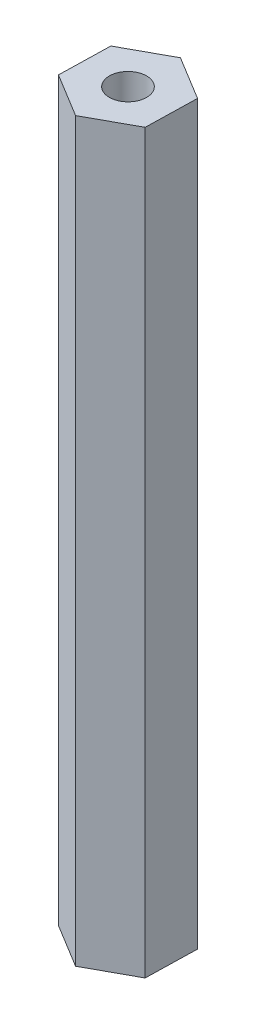
SolidWorks part; units mm, degrees
material "AISI 316 Annealed Stainless Steel Bar (SS)"
ref_plane "Front Plane" through (0, 0, 0) normal (0, 0, 1) x (1, 0, 0)
ref_plane "Top Plane" through (0, 0, 0) normal (0, 1, 0) x (1, 0, 0)
ref_plane "Right Plane" through (0, 0, 0) normal (1, 0, 0) x (0, 0, -1)
sketch "Sketch1" plane through (0, 0, 0) normal (0, 1, 0) x (1, 0, 0)
  line L1 (5.0651, 2.7709) -> (0.1329, 5.772)
  line L2 (0.1329, 5.772) -> (-4.9322, 3.0011)
  line L3 (-4.9322, 3.0011) -> (-5.0651, -2.7709)
  line L4 (-5.0651, -2.7709) -> (-0.1329, -5.772)
  line L5 (-0.1329, -5.772) -> (4.9322, -3.0011)
  line L6 (4.9322, -3.0011) -> (5.0651, 2.7709)
  circle A0 centre (0, 0) radius 5 construction
  circle A1 centre (0, 0) radius 2.1
  dimension "D2" = 4.2
  dimension "D1" = 10
extrude "Boss-Extrude1" add sketch "Sketch1" along normal mid plane 83 contours L1 L2 L3 L4 L5 L6
extrude "Cut-Extrude1" cut sketch "Sketch1<3>" against normal through all from offset 41.5 contours A1 region at (0, 0, 0)
sketch "Sketch1<3>" plane through (0, 0, 0) normal (0, 1, 0) x (1, 0, 0) same geometry as "Sketch1"
cosmetic thread "Cosmetic Thread1" parameters "D1"=15, "D2"=5
cosmetic thread "Cosmetic Thread2" parameters "D1"=15, "D2"=5
